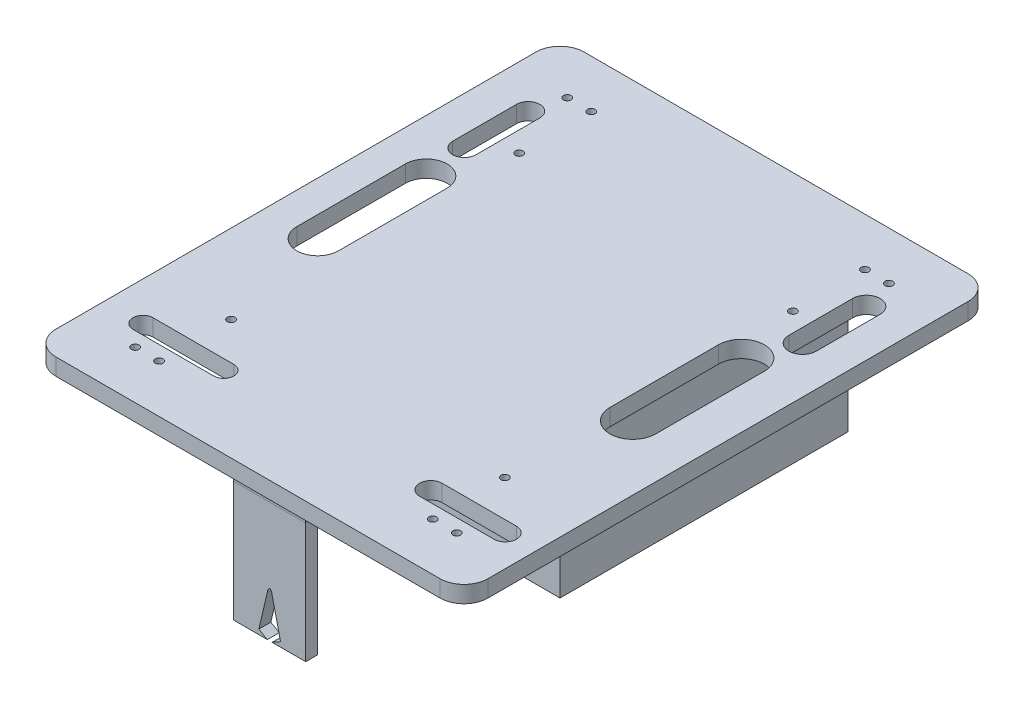
SolidWorks part; units mm, degrees
ref_plane "前视基准面" through (0, 0, 0) normal (0, 0, 1) x (1, 0, 0)
ref_plane "上视基准面" through (0, 0, 0) normal (0, 1, 0) x (1, 0, 0)
ref_plane "右视基准面" through (0, 0, 0) normal (1, 0, 0) x (0, 0, -1)
sketch "草图1" plane through (0, 0, 0) normal (0, 1, 0) x (1, 0, 0)
  line L0 (-95.2597, 129.0909) -> (-62.2597, 129.0909) construction
  line L1 (-85.2597, 139.0909) -> (74.7403, 139.0909)
  line L2 (-95.2597, 129.0909) -> (-95.2597, -70.9091)
  line L3 (-85.2597, -80.9091) -> (74.7403, -80.9091)
  line L4 (84.7403, 129.0909) -> (84.7403, -70.9091)
  line L5 (-62.2597, 139.0909) -> (-62.2597, 89.0909) construction
  line L6 (84.7403, 129.0909) -> (51.7403, 129.0909) construction
  line L7 (51.7403, 139.0909) -> (51.7403, 89.0909) construction
  line L8 (-95.2597, -70.9091) -> (-62.2597, -70.9091) construction
  line L9 (-62.2597, -80.9091) -> (-62.2597, -30.9091) construction
  line L10 (84.7403, -70.9091) -> (51.7403, -70.9091) construction
  line L11 (51.7403, -70.9091) -> (51.7403, -80.9091) construction
  line L12 (51.7403, -80.9091) -> (51.7403, -30.9091) construction
  arc A0 (-85.2597, 139.0909) -> (-95.2597, 129.0909) centre (-85.2597, 129.0909) ccw
  arc A1 (74.7403, 139.0909) -> (84.7403, 129.0909) centre (74.7403, 129.0909) cw
  arc A2 (74.7403, -80.9091) -> (84.7403, -70.9091) centre (74.7403, -70.9091) ccw
  arc A3 (-95.2597, -70.9091) -> (-85.2597, -80.9091) centre (-85.2597, -70.9091) ccw
  circle A4 centre (-62.2597, 89.0909) radius 1.6
  circle A5 centre (51.7403, 89.0909) radius 1.6
  circle A6 centre (-62.2597, -30.9091) radius 1.6
  circle A7 centre (51.7403, -30.9091) radius 1.6
  point P6 (-95.2597, 139.0909)
  point P9 (84.7403, 139.0909)
  point P14 (-95.2597, -80.9091)
  dimension "D3" = 10
  dimension "D4" = 10
  dimension "D5" = 10
  dimension "D6" = 10
  dimension "D1" = 180
  dimension "D2" = 220
extrude "凸台-拉伸1" add sketch "草图1" along normal blind 7
sketch "草图2" plane through (0, 0, 0) normal (0, -1, 0) x (1, 0, 0)
  line L0 (-5.2597, 80.9091) -> (-5.2597, -139.0909) construction
  line L1 (-85.2597, 80.9091) -> (74.7403, 80.9091) construction
  line L2 (74.7403, -139.0909) -> (-85.2597, -139.0909) construction
  line L3 (-95.2597, -29.0909) -> (84.7403, -29.0909) construction
  line L4 (-95.2597, -129.0909) -> (-95.2597, 70.9091) construction
  line L5 (84.7403, 70.9091) -> (84.7403, -129.0909) construction
  line L6 (-5.2597, -29.0909) -> (-45.2597, -29.0909) construction
  line L7 (-5.2597, -29.0909) -> (34.7403, -29.0909) construction
  line L8 (-45.2597, -29.0909) -> (-45.2597, -119.0909) construction
  line L9 (-45.2597, -119.0909) -> (34.7403, -119.0909) construction
  line L10 (34.7403, -119.0909) -> (34.7403, -29.0909) construction
  line L11 (34.7403, -29.0909) -> (-45.2597, -29.0909) construction
  line L12 (-45.2597, -29.0909) -> (-45.2597, -9.0909) construction
  line L13 (-45.2597, -9.0909) -> (34.7403, -9.0909) construction
  line L14 (34.7403, -9.0909) -> (34.7403, -29.0909) construction
  line L15 (-45.2597, -9.0909) -> (-50.2597, -9.0909) construction
  line L16 (34.7403, -9.0909) -> (-45.2597, -9.0909)
  line L17 (34.7403, -9.0909) -> (34.7403, -119.0909)
  line L18 (34.7403, -119.0909) -> (-45.2597, -119.0909)
  line L19 (-45.2597, -9.0909) -> (-45.2597, -119.0909)
  line L20 (-45.2597, -9.0909) -> (-45.2597, -4.0909) construction
  line L21 (34.7403, -119.0909) -> (34.7403, -124.0909) construction
  line L22 (34.7403, -119.0909) -> (39.7403, -119.0909) construction
  line L24 (39.7403, -124.0909) -> (-50.2597, -124.0909)
  line L25 (39.7403, -124.0909) -> (39.7403, -4.0909)
  line L26 (39.7403, -4.0909) -> (-50.2597, -4.0909)
  line L27 (-50.2597, -124.0909) -> (-50.2597, -4.0909)
extrude "凸台-拉伸2" add sketch "草图2" along normal blind 60
sketch "草图3" plane through (0, 0, 0) normal (0, -1, 0) x (1, 0, 0)
  line L0 (-5.2597, 80.9091) -> (-5.2597, 7.1374) construction
  line L1 (-85.2597, 80.9091) -> (74.7403, 80.9091) construction
  line L2 (-5.2597, 7.1374) -> (-30.2597, 7.1374) construction
  line L3 (-5.2597, 7.1374) -> (19.7403, 7.1374) construction
  line L4 (-30.2597, 7.1374) -> (-30.2597, 37.1374) construction
  line L5 (-30.2597, 37.1374) -> (19.7403, 37.1374) construction
  line L6 (19.7403, 37.1374) -> (19.7403, 7.1374) construction
  line L7 (-30.2597, 37.1374) -> (-33.2597, 37.1374) construction
  line L8 (-30.2597, 7.1374) -> (19.7403, 7.1374)
  line L9 (-30.2597, 7.1374) -> (-30.2597, 37.1374)
  line L10 (-30.2597, 37.1374) -> (19.7403, 37.1374)
  line L11 (19.7403, 7.1374) -> (19.7403, 37.1374)
  line L12 (-30.2597, 37.1374) -> (-30.2597, 40.1374) construction
  line L13 (19.7403, 7.1374) -> (19.7403, 4.1374) construction
  line L14 (19.7403, 7.1374) -> (22.7403, 7.1374) construction
  line L16 (-33.2597, 40.1374) -> (22.7403, 40.1374)
  line L17 (-33.2597, 40.1374) -> (-33.2597, 4.1374)
  line L18 (-33.2597, 4.1374) -> (22.7403, 4.1374)
  line L19 (22.7403, 40.1374) -> (22.7403, 4.1374)
extrude "凸台-拉伸3" add sketch "草图3" along normal blind 10
sketch "草图5" plane through (0, -10, 0) normal (0, -1, 0) x (1, 0, 0)
  line L0 (-33.2597, 4.1374) -> (-33.2597, 7.1374)
  line L1 (-33.2597, 40.1374) -> (-33.2597, 4.1374) construction
  line L2 (-33.2597, 7.1374) -> (22.7403, 7.1374)
  line L3 (22.7403, 4.1374) -> (22.7403, 40.1374) construction
  line L4 (22.7403, 7.1374) -> (22.7403, 4.1374)
  line L5 (22.7403, 4.1374) -> (-33.2597, 4.1374)
extrude "凸台-拉伸4" add sketch "草图5" along normal blind 20
sketch "草图6" plane through (0, 0, 0) normal (0, -1, 0) x (1, 0, 0)
  line L0 (-5.2597, 80.9091) -> (-5.2597, 71.8328) construction
  line L1 (-85.2597, 80.9091) -> (74.7403, 80.9091) construction
  line L2 (-5.2597, 71.8328) -> (-5.2597, 66.8328) construction
  line L3 (-5.2597, 66.8328) -> (9.7403, 66.8328) construction
  line L4 (-5.2597, 66.8328) -> (-20.2597, 66.8328) construction
  line L5 (-20.2597, 66.8328) -> (-20.2597, 71.8328) construction
  line L6 (-20.2597, 71.8328) -> (9.7403, 71.8328) construction
  line L8 (9.7403, 71.8328) -> (-20.2597, 71.8328)
  line L9 (9.7403, 71.8328) -> (9.7403, 66.8328)
  line L10 (9.7403, 66.8328) -> (-20.2597, 66.8328)
  line L11 (-20.2597, 71.8328) -> (-20.2597, 66.8328)
extrude "凸台-拉伸5" add sketch "草图6" along normal blind 60
sketch "草图8" plane through (0, 0, 71.8328) normal (0, 0, 1) x (1, 0, 0)
  line L0 (9.7403, -60) -> (-3.7597, -60) construction
  line L1 (9.7403, -60) -> (-20.2597, -60) construction
  line L2 (-20.2597, -60) -> (-6.7597, -60) construction
  line L3 (-5.2597, 0) -> (-5.2597, -60) construction
  line L4 (9.7403, 0) -> (-20.2597, 0) construction
  line L5 (-5.2597, -60) -> (-5.2597, -41) construction
  line L6 (-5.2597, -60) -> (-10.2597, -60) construction
  line L7 (-5.2597, -60) -> (-0.2597, -60) construction
  line L8 (-5.2597, -41) -> (-6.2597, -41) construction
  line L9 (-5.2597, -41) -> (-4.2597, -41) construction
  line L10 (-5.2597, -41) -> (-5.2597, -43) construction
  line L11 (-5.2597, -43) -> (-6.2597, -43) construction
  line L12 (-6.2597, -43) -> (-5.2597, -43) construction
  line L13 (-5.2597, -43) -> (-4.2597, -43) construction
  line L14 (-6.2597, -43) -> (-10.2597, -60)
  line L15 (-4.2597, -43) -> (-0.2597, -60)
  line L16 (-10.2597, -60) -> (-0.2597, -60)
  arc A0 (-6.2597, -43) -> (-5.2597, -41) centre (-3.7597, -43) cw
  arc A1 (-4.2597, -43) -> (-5.2597, -41) centre (-6.7597, -43) ccw
  dimension "D1" = 2
extrude "切除-拉伸1" cut sketch "草图8" against normal blind 10
sketch "草图9" plane through (0, 0, 71.8328) normal (0, 0, 1) x (1, 0, 0)
  line L0 (-10.2597, -60) -> (-6.2597, -60) construction
  line L1 (39.7403, -60) -> (-50.2597, -60) construction
  line L2 (-0.2597, -60) -> (-4.2597, -60) construction
  line L3 (-6.2597, -60) -> (-6.2597, -58) construction
  line L4 (-4.2597, -60) -> (-4.2597, -58) construction
  line L5 (-6.2597, -60) -> (-9.7892, -58)
  line L6 (-6.2597, -43) -> (-10.2597, -60) construction
  line L7 (-9.7892, -58) -> (-10.2597, -60)
  line L8 (-10.2597, -60) -> (-6.2597, -60)
  line L9 (-4.2597, -60) -> (-0.2597, -60)
  line L10 (-4.2597, -60) -> (-0.7303, -58)
  line L11 (-0.2597, -60) -> (-4.2597, -43) construction
  line L12 (-0.7303, -58) -> (-0.2597, -60)
extrude "凸台-拉伸6" add sketch "草图9" against normal blind 5
sketch "草图10" plane through (0, 0, 0) normal (0, -1, 0) x (1, 0, 0)
  line L0 (-73.3698, -16.2598) -> (-73.3698, -61.4888) construction
  line L1 (-64.659, -16.2598) -> (-64.659, -61.4888)
  line L2 (-82.0806, -16.2598) -> (-82.0806, -61.4888)
  line L3 (57.9069, -16.2598) -> (57.9069, -61.4888) construction
  line L4 (67.4592, -16.2598) -> (67.4592, -61.4888)
  line L5 (48.3545, -16.2598) -> (48.3545, -61.4888)
  arc A0 (-64.659, -16.2598) -> (-82.0806, -16.2598) centre (-73.3698, -16.2598) ccw
  arc A1 (-82.0806, -61.4888) -> (-64.659, -61.4888) centre (-73.3698, -61.4888) ccw
  arc A2 (67.4592, -16.2598) -> (48.3545, -16.2598) centre (57.9069, -16.2598) ccw
  arc A3 (48.3545, -61.4888) -> (67.4592, -61.4888) centre (57.9069, -61.4888) ccw
  point P2 (-73.3698, -38.8743)
  point P9 (57.9069, -38.8743)
extrude "切除-拉伸2" cut sketch "草图10" against normal blind 10
sketch "草图13" plane through (0, 7, 0) normal (0, 1, 0) x (1, 0, 0)
  line L0 (-95.2597, 129.0909) -> (-62.2597, 129.0909) construction
  line L1 (-62.2597, 139.0909) -> (-62.2597, 119.0909) construction
  line L2 (74.7403, 139.0909) -> (-85.2597, 139.0909) construction
  line L3 (84.7403, 129.0909) -> (51.7403, 129.0909) construction
  line L4 (51.7403, 139.0909) -> (51.7403, 119.0909) construction
  line L5 (-95.2597, -70.9091) -> (-62.2597, -70.9091) construction
  line L6 (-62.2597, -80.9091) -> (-62.2597, -60.9091) construction
  line L7 (-85.2597, -80.9091) -> (74.7403, -80.9091) construction
  line L8 (74.7403, -80.9091) -> (74.7403, -60.9091) construction
  line L9 (84.7403, -60.9091) -> (51.7403, -60.9091) construction
  line L10 (84.7403, -70.9091) -> (84.7403, 129.0909) construction
  circle A0 centre (-62.2597, 119.0909) radius 1.6
  circle A1 centre (51.7403, 119.0909) radius 1.6
  circle A2 centre (-62.2597, -60.9091) radius 1.6
  circle A3 centre (51.7403, -60.9091) radius 1.6
  dimension "D1" = 33
extrude "切除-拉伸5" cut sketch "草图13" against normal blind 10
sketch "草图14" plane through (0, 0, 0) normal (0, -1, 0) x (-1, 0, 0)
  line L0 (79.1701, -50.7267) -> (45.4996, -50.7267) construction
  line L1 (79.1701, -54.9146) -> (45.4996, -54.9146)
  line L2 (79.1701, -46.5389) -> (45.4996, -46.5389)
  line L3 (-40.7705, -50.7267) -> (-71.7608, -50.7267) construction
  line L4 (-40.7705, -55.4171) -> (-71.7608, -55.4171)
  line L5 (-40.7705, -46.0363) -> (-71.7608, -46.0363)
  arc A0 (79.1701, -54.9146) -> (79.1701, -46.5389) centre (79.1701, -50.7267) ccw
  arc A1 (45.4996, -46.5389) -> (45.4996, -54.9146) centre (45.4996, -50.7267) ccw
  arc A2 (-40.7705, -55.4171) -> (-40.7705, -46.0363) centre (-40.7705, -50.7267) ccw
  arc A3 (-71.7608, -46.0363) -> (-71.7608, -55.4171) centre (-71.7608, -50.7267) ccw
  point P2 (62.3348, -50.7267)
  point P7 (-56.2656, -50.7267)
extrude "切除-拉伸6" cut sketch "草图14" against normal blind 10
sketch "草图16" plane through (0, 0, -124.0909) normal (0, 0, -1) x (-1, 0, 0)
  line L0 (6.2597, -60) -> (6.2597, -50) construction
  line L1 (50.2597, -60) -> (50.2597, -55) construction
  line L2 (50.2597, -60) -> (50.2597, 0) construction
  line L3 (50.2597, -55) -> (40.2597, -55) construction
  line L4 (-39.7403, -55) -> (-29.7403, -55) construction
  line L5 (-39.7403, -60) -> (-39.7403, 0) construction
  line L7 (-29.7403, -55) -> (40.2597, -55)
  line L8 (-29.7403, -55) -> (-29.7403, -50)
  line L9 (-29.7403, -50) -> (40.2597, -50)
  line L10 (40.2597, -55) -> (40.2597, -50)
extrude "切除-拉伸7" cut sketch "草图16" against normal blind 10
fillet "圆角1" radius 10 1 edges at (-5.2597, 0, 71.8328)
fillet "圆角2" radius 10 1 edges at (-5.2597, 0, 66.8328)
fillet "圆角3" radius 10 1 edges at (-20.2597, 0, 68.8709)
fillet "圆角4" radius 10 1 edges at (9.7403, 0, 68.8709)
sketch "草图18" plane through (0, 7, 0) normal (0, 1, 0) x (1, 0, 0)
  line L0 (-62.2597, 119.0909) -> (-72.2597, 119.0909) construction
  line L1 (51.7403, 119.0909) -> (61.7403, 119.0909) construction
  line L2 (-62.2597, -60.9091) -> (-72.2597, -60.9091) construction
  line L3 (51.7403, -60.9091) -> (61.7403, -60.9091) construction
  circle A0 centre (-72.2597, 119.0909) radius 1.6
  circle A1 centre (61.7403, 119.0909) radius 1.6
  circle A2 centre (-72.2597, -60.9091) radius 1.6
  circle A3 centre (61.7403, -60.9091) radius 1.6
extrude "切除-拉伸8" cut sketch "草图18" against normal blind 10
sketch "草图19" plane through (0, 0, 0) normal (0, -1, 0) x (1, 0, 0)
  line L0 (-75.5573, -79.552) -> (-75.5573, -106.1331) construction
  line L1 (-70.6785, -79.552) -> (-70.6785, -106.1331)
  line L2 (-80.4361, -79.552) -> (-80.4361, -106.1331)
  line L3 (65.3299, -79.552) -> (65.3299, -106.1331) construction
  line L4 (71.0516, -79.552) -> (71.0516, -106.1331)
  line L5 (59.6082, -79.552) -> (59.6082, -106.1331)
  arc A0 (-70.6785, -79.552) -> (-80.4361, -79.552) centre (-75.5573, -79.552) ccw
  arc A1 (-80.4361, -106.1331) -> (-70.6785, -106.1331) centre (-75.5573, -106.1331) ccw
  arc A2 (71.0516, -79.552) -> (59.6082, -79.552) centre (65.3299, -79.552) ccw
  arc A3 (59.6082, -106.1331) -> (71.0516, -106.1331) centre (65.3299, -106.1331) ccw
  point P2 (-75.5573, -92.8425)
  point P7 (65.3299, -92.8425)
extrude "切除-拉伸9" cut sketch "草图19" against normal blind 10
fillet "圆角5" radius 10 1 edges at (-5.2597, 0, 40.1374)
fillet "圆角6" radius 10 1 edges at (-33.2597, 0, 27.1374)
fillet "圆角7" radius 10 1 edges at (22.7403, 0, 27.1374)
fillet "圆角9" radius 10 1 edges at (-5.2597, 0, 4.1374)
